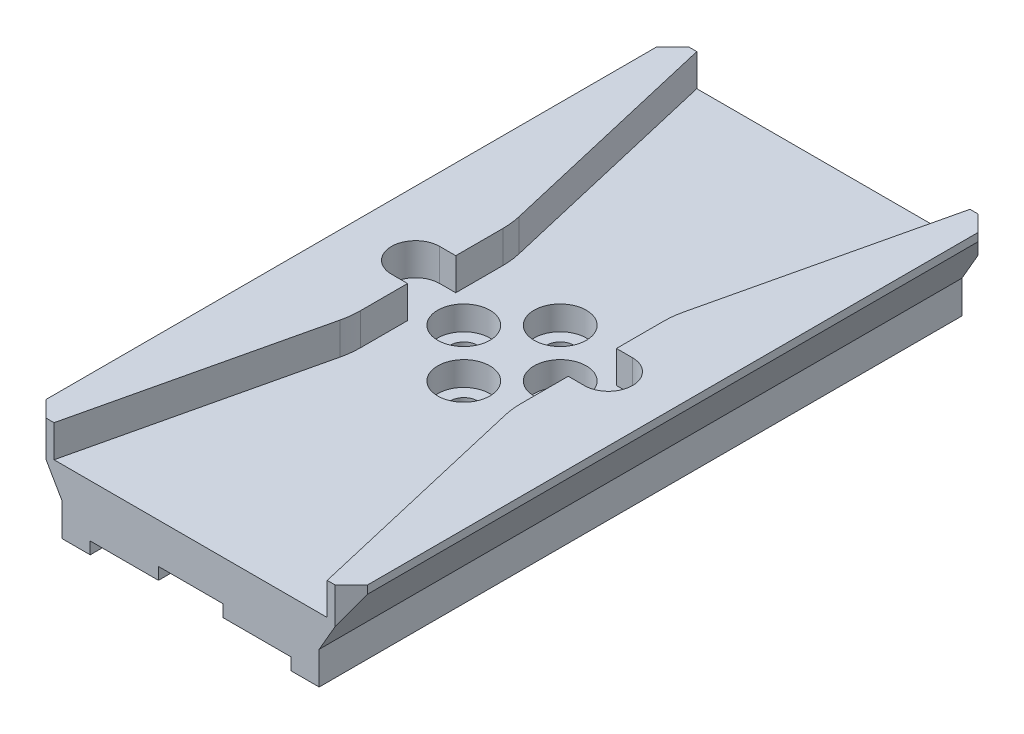
SolidWorks part; units mm, degrees
material "Сплав 2024"
ref_plane "Спереди" through (0, 0, 0) normal (0, 0, 1) x (1, 0, 0)
ref_plane "Сверху" through (0, 0, 0) normal (0, 1, 0) x (1, 0, 0)
ref_plane "Справа" through (0, 0, 0) normal (1, 0, 0) x (0, 0, -1)
sketch "Эскиз1" plane through (0, 0, 0) normal (0, 0, 1) x (1, 0, 0)
  line L0 (-20, 5) -> (-16, -1.9282)
  line L1 (-20, 6) -> (20, 6)
  line L2 (-25.6942, 6) -> (28.5829, 6) construction
  line L3 (-16, -6) -> (16, -6)
  line L4 (0, 6) -> (0, -6) construction
  line L5 (-22.304, 8.9907) -> (-15.6808, -2.4811) construction
  line L7 (-16, -1.9282) -> (-16, -6)
  line L9 (-20, 6) -> (-20, 5)
  line L10 (16, -1.9282) -> (16, -6)
  line L11 (20, 5) -> (16, -1.9282)
  line L12 (20, 6) -> (20, 5)
  point P15 (-20.5774, 6)
  dimension "D1" = 16
  dimension "D2" = 12
  dimension "D3" = 60
  dimension "D4" = 20.5774
  dimension "D6" = 20
  dimension "D7" = 1
extrude "Бобышка-Вытянуть1" add sketch "Эскиз1" along normal blind 80
sketch "Эскиз2" plane through (0, 6, 0) normal (0, 1, 0) x (1, 0, 0)
  line L0 (0, 0) -> (0, -80) construction
  line L1 (20, 0) -> (-20, 0) construction
  line L2 (20, -80) -> (-20, -80) construction
  line L3 (-17, 0) -> (-17, -80) construction
  line L4 (10, -50) -> (17, -80)
  line L5 (-17, 0) -> (-10, -30)
  line L6 (-10, -30) -> (-10, -50)
  line L7 (-10, -50) -> (-17, -80)
  line L8 (10, -30) -> (10, -50)
  line L9 (17, 0) -> (10, -30)
  line L10 (20, -40) -> (-20, -40) construction
  line L11 (-17, 0) -> (17, 0)
  line L12 (17, -80) -> (-17, -80)
  line L20 (-20, -80) -> (-20, 0) construction
  line L21 (20, -80) -> (20, 0) construction
  point P24 (-10, -40)
  dimension "D1" = 10
  dimension "D2" = 3
  dimension "D3" = 20
extrude "Вырез-Вытянуть1" cut sketch "Эскиз2" against normal blind 4
sketch "Эскиз3" plane through (0, 6, 0) normal (0, 1, 0) x (1, 0, 0)
  line L0 (20, -40) -> (-20, -40) construction
  line L4 (-10, -37) -> (-15, -37)
  line L5 (-10, -37) -> (-10, -43)
  line L6 (-10, -43) -> (-15, -43)
  line L7 (-15, -37) -> (-15, -43)
  line L8 (0, 0) -> (0, -80) construction
  line L9 (17, 0) -> (-17, 0) construction
  line L10 (-17, -80) -> (17, -80) construction
  line L11 (10, -37) -> (10, -43)
  line L12 (10, -43) -> (15, -43)
  line L13 (15, -37) -> (15, -43)
  line L14 (10, -37) -> (15, -37)
  line L15 (-10, -30) -> (-10, -50) construction
  line L16 (20, -80) -> (20, 0) construction
  line L17 (-20, -80) -> (-20, 0) construction
  point P12 (-10, -40)
  dimension "D1" = 6
  dimension "D2" = 5
extrude "Вырез-Вытянуть2" [suppressed] cut sketch "Эскиз3" against normal blind 4
fillet "Скругление1" [suppressed] radius 1.5
fillet "Скругление2" radius 10 4 edges at (10, 4, 50) (10, 4, 30) (-10, 4, 30) (-10, 4, 50)
sketch "Эскиз4" plane through (0, 2, 0) normal (0, 1, 0) x (1, 0, 0)
  line L0 (0, 0) -> (0, -80) construction
  line L1 (-17, -80) -> (17, -80) construction
  line L2 (20, -40) -> (-20, -40) construction
  line L5 (20, -80) -> (20, 0) construction
  line L6 (-20, -80) -> (-20, 0) construction
  circle A0 centre (0, -40) radius 6 construction
  dimension "D1" = 12
hole_wizard "Цековка для винта с внутренним шестигранником M31" positions "Эскиз6" profile "Эскиз5" counterbore size "M3" standard "Ansi Metric" end condition through all
sketch "Эскиз6" plane through (0, 2, 0) normal (0, 1, 0) x (1, 0, 0)
  line L0 (0, 0) -> (0, -80) construction
  line L1 (20, -40) -> (-20, -40) construction
  circle A0 centre (0, -40) radius 6 construction
  point P0 (0, -34)
  point P2 (6, -40)
  point P4 (0, -46)
  point P6 (-6, -40)
sketch "Эскиз5" plane through (0, 2, 34) normal (1, 0, 0) x (0, 0, 1)
  line L0 (0, 0) -> (0, 8)
  line L1 (0, 8) -> (1.7, 8)
  line L3 (1.7, 8) -> (1.7, 3)
  line L4 (1.7, 3) -> (3.25, 3)
  line L5 (3.25, 3) -> (3.25, 0)
  line L7 (3.25, 0) -> (0, 0)
  line L11 (0, -6.35) -> (0, 107.95) construction
  dimension "Диаметр сквозного отверстия" = 3.4
  dimension "Глубина сквозного отверстия" = 8
  dimension "Диаметр цековки" = 6.5
  dimension "Глубина цековки" = 3
sketch "Эскиз7" plane through (0, -6, 0) normal (0, -1, 0) x (1, 0, 0)
  line L0 (0, 80) -> (0, 0) construction
  line L2 (-11.5, 77) -> (11.5, 77)
  line L3 (-11.5, 77) -> (-11.5, 51)
  line L5 (-16, 80) -> (16, 80) construction
  line L6 (11.5, 77) -> (11.5, 51)
  line L7 (-11.5, 77) -> (11.5, 51) construction
  line L8 (-11.5, 51) -> (11.5, 77) construction
  arc A0 (-11.5, 51) -> (11.5, 51) centre (0, 19) cw
  point P0 (0, 64)
  dimension "D2" = 26
  dimension "D5" = 45
  dimension "D1" = 3
  dimension "D3" = 23
  dimension "D4" = 26
extrude "Вырез-Вытянуть3" cut sketch "Эскиз7" against normal blind 7
sketch "Эскиз8" plane through (0, 1, 0) normal (0, -1, 0) x (1, 0, 0)
  line L0 (0, 80) -> (0, 0) construction
  line L1 (-16, 80) -> (16, 80) construction
  line L2 (-16, 61.2) -> (16, 61.2) construction
  line L3 (-16, 80) -> (-16, 0) construction
  line L4 (16, 80) -> (16, 0) construction
  line L6 (13.1, 58.95) -> (7.1, 63.45) construction
  line L7 (-13.1, 63.45) -> (-7.1, 63.45)
  line L8 (-13.1, 63.45) -> (-13.1, 58.95)
  line L9 (-13.1, 58.95) -> (-7.1, 58.95)
  line L10 (13.1, 63.45) -> (7.1, 58.95) construction
  line L11 (-13.1, 63.45) -> (-7.1, 58.95) construction
  line L12 (-13.1, 58.95) -> (-7.1, 63.45) construction
  line L13 (13.1, 58.95) -> (7.1, 58.95)
  line L14 (13.1, 63.45) -> (13.1, 58.95)
  line L15 (13.1, 63.45) -> (7.1, 63.45)
  arc A0 (-7.1, 58.95) -> (-7.1, 63.45) centre (-7.1, 61.2) ccw
  arc A1 (7.1, 58.95) -> (7.1, 63.45) centre (7.1, 61.2) cw
  point P17 (-10.1, 61.2)
  point P24 (10.1, 61.2)
  dimension "D1" = 7.1
  dimension "D2" = 4.5
  dimension "D3" = 10.2
  dimension "D4" = 3
extrude "Бобышка-Вытянуть2" add sketch "Эскиз8" along normal blind 3
hole_wizard "Отверстие обработанное метчиком M2.5x0.451" positions "Эскиз10" profile "Эскиз9" tap size "M2.5x0.45" standard "Ansi Metric"
sketch "Эскиз10" plane through (0, -2, 0) normal (0, -1, 0) x (-1, 0, 0)
  point P0 (7.1, -61.2)
  point P2 (-7.1, -61.2)
sketch "Эскиз9" plane through (-7.1, -2, 61.2) normal (1, 0, 0) x (0, 0, -1)
  line L0 (0, 0) -> (0, 3.6159)
  line L1 (0, 3.6159) -> (1.025, 3)
  line L2 (1.025, 3) -> (1.025, 0)
  line L5 (1.025, 0) -> (0, 0)
  line L10 (0, 3.6159) -> (-1.025, 3) construction
  line L11 (0, -6.35) -> (0, 107.95) construction
  dimension "Диаметр сверла" = 2.05
  dimension "Глубина сверла" = 3
  dimension "Угол заточки сверла" = 118
cosmetic thread "Отверстие резьбы7" parameters "D1"=3, "D2"=2.5
cosmetic thread "Отверстие резьбы8" parameters "D1"=3, "D2"=2.5
sketch "Эскиз12" plane through (0, 1, 0) normal (0, -1, 0) x (1, 0, 0)
  line L0 (0, 77) -> (0, 51) construction
  line L1 (11.5, 77) -> (-11.5, 77) construction
  line L2 (-11.5, 51) -> (11.5, 51) construction
  line L3 (-1.8247, 64) -> (1.8247, 64) construction
  line L4 (-13.6614, 76) -> (7.1704, 76) construction
  line L5 (-11.5, 80.8402) -> (-11.5, 69.1924) construction
  line L6 (-11.5, 77) -> (-11.5, 51) construction
  circle A0 centre (-11.5, 76) radius 2
  circle A3 centre (11.5, 76) radius 2
  circle A4 centre (11.5, 52) radius 2
  circle A6 centre (-11.5, 52) radius 2
  point P14 (0, 64)
  dimension "D3" = 4
  dimension "D2" = 1
sketch "Эскиз15" plane through (0, 1, 0) normal (0, -1, 0) x (1, 0, 0)
  line L0 (0, 77) -> (0, 51) construction
  line L1 (11.5, 77) -> (-11.5, 77) construction
  line L2 (-13.8501, 64) -> (13.8501, 64) construction
  line L4 (-11.5, 51) -> (11.5, 51) construction
  line L5 (11.5, 51) -> (11.5, 77) construction
  line L7 (11.5, 77) -> (-11.5, 77) construction
  line L8 (-11.5, 77) -> (-11.5, 63.45) construction
  line L9 (-11.5, 77) -> (-11.5, 51) construction
  circle A0 centre (-11.5, 51) radius 2.5
  circle A1 centre (11.5, 51) radius 2.5
  circle A2 centre (-9, 77) radius 2.5
  circle A3 centre (9, 77) radius 2.5
  point P8 (0, 64)
  dimension "D1" = 5
  dimension "D2" = 5
  dimension "D3" = 5
extrude "Бобышка-Вытянуть5" add sketch "Эскиз15" along normal up to surface (7 mm away) up to face at (0, -6, 64.5009)
fillet "Скругление8" radius 3 12 edges at (11.5, -2.5, 53.5) (9.1178, -2.5, 51.7584) (-9.1178, -2.5, 51.7584) (-11.5, -2.5, 53.5) (-11.5, -0.5, 58.95) (11.5, -0.5, 58.95) (11.5, -0.5, 63.45) (-11.5, -0.5, 63.45) (-11.5, -2.5, 77) (11.5, -2.5, 77) (6.5, -2.5, 77) (-6.5, -2.5, 77)
sketch "Эскиз16" plane through (0, -6, 0) normal (0, -1, 0) x (1, 0, 0)
  line L0 (-16, 80) -> (16, 80) construction
  line L1 (-12.5, 80) -> (12.5, 80)
  line L70 (-12.5, 54.3541) -> (-12.5, 80)
  line L71 (12.5, 54.3541) -> (12.5, 80)
  line L72 (-11.5, 71.5228) -> (-11.5, 55.6098) construction
  line L73 (11.5, 55.6098) -> (11.5, 71.5228) construction
  arc A0 (7.2531, 52.2211) -> (-7.2531, 52.2211) centre (0, 19) ccw construction
  arc A1 (7.2531, 52.2211) -> (-7.2531, 52.2211) centre (0, 19) ccw construction
  arc A2 (8.0001, 51.0194) -> (-8.0001, 51.0194) centre (0, 19) ccw
  arc A3 (7.0398, 51.2441) -> (-7.0398, 51.2441) centre (0, 19) ccw construction
  arc A42 (-12.5, 54.3541) -> (-8.0001, 51.0194) centre (-11.5, 51) ccw
  arc A43 (8.0001, 51.0194) -> (12.5, 54.3541) centre (11.5, 51) ccw
  dimension "D3" = 7
  dimension "D4" = 7
  dimension "D6" = 1
  dimension "D7" = 1
  dimension "D2" = 1
extrude "Вырез-Вытянуть6" cut sketch "Эскиз16" against normal blind 1.5
fillet "Скругление9" radius 3 4 edges at (12.5, -5.25, 54.3541) (8.0001, -5.25, 51.0194) (-8.0001, -5.25, 51.0194) (-12.5, -5.25, 54.3541)
hole_wizard "Отверстие обработанное метчиком M3x0.52" positions "Эскиз19" profile "Эскиз18" tap size "M3x0.5" standard "Ansi Metric"
sketch "Эскиз19" plane through (0, -4.5, 0) normal (0, -1, 0) x (-1, 0, 0)
  point P0 (11.5, -51)
  point P3 (-11.5, -51)
  point P6 (-9, -77)
  point P9 (9, -77)
sketch "Эскиз18" plane through (-11.5, -4.5, 51) normal (1, 0, 0) x (0, 0, -1)
  line L0 (0, 0) -> (0, 6.2501)
  line L1 (0, 6.2501) -> (1.25, 5.499)
  line L2 (1.25, 5.499) -> (1.25, 0)
  line L5 (1.25, 0) -> (0, 0)
  line L10 (0, 6.2501) -> (-1.25, 5.499) construction
  line L11 (0, -6.35) -> (0, 107.95) construction
  dimension "Диаметр сверла" = 2.5
  dimension "Глубина сверла" = 5.499
  dimension "Угол заточки сверла" = 118
cosmetic thread "Отверстие резьбы9" parameters "D1"=5.5, "D2"=3
cosmetic thread "Отверстие резьбы10" parameters "D1"=5.5, "D2"=3
cosmetic thread "Отверстие резьбы11" parameters "D1"=5.5, "D2"=3
cosmetic thread "Отверстие резьбы12" parameters "D1"=5.5, "D2"=3
sketch "Эскиз20" plane through (0, -4.5, 0) normal (0, -1, 0) x (1, 0, 0)
  line L0 (0, 80) -> (0, 67.2176) construction
  line L1 (12.5, 80) -> (-12.5, 80) construction
  line L2 (-4.3902, 77) -> (4.3902, 77) construction
  line L3 (-4, 80) -> (4, 80)
  line L4 (-4, 80) -> (-4, 77)
  line L5 (-4, 77) -> (4, 77)
  line L6 (4, 80) -> (4, 77)
  line L7 (-4, 80) -> (4, 77) construction
  line L8 (-4, 77) -> (4, 80) construction
  point P5 (0, 78.5)
  dimension "D1" = 8
extrude "Вырез-Вытянуть7" cut sketch "Эскиз20" against normal blind 1.5
sketch "Эскиз21" plane through (0, -2, 0) normal (0, -1, 0) x (1, 0, 0)
  line L0 (11.5, 61.2) -> (-11.5, 61.2) construction
  line L1 (11.5, 55.95) -> (11.5, 66.45) construction
  line L2 (-11.5, 55.95) -> (-11.5, 66.45) construction
  line L3 (0, 53.0037) -> (0, 77) construction
  line L4 (4.3902, 77) -> (-4.3902, 77) construction
  line L6 (-5.5, 63.7) -> (5.5, 63.7)
  line L7 (-5.5, 63.7) -> (-5.5, 58.7)
  line L8 (-5.5, 58.7) -> (5.5, 58.7)
  line L9 (5.5, 63.7) -> (5.5, 58.7)
  line L10 (-5.5, 63.7) -> (5.5, 58.7) construction
  line L11 (-5.5, 58.7) -> (5.5, 63.7) construction
  arc A0 (7.2531, 52.2211) -> (-7.2531, 52.2211) centre (0, 19) ccw construction
  point P13 (0, 61.2)
  dimension "D1" = 11
  dimension "D2" = 5
extrude "Вырез-Вытянуть8" cut sketch "Эскиз21" against normal up to surface (3 mm away) up to face at (0, 1, 62.8736)
ref_plane "Плоскость1" through (0, 0, 40) normal (0, 0, 1) x (1, 0, 0)
mirror "Зеркальное отражение1" about plane through (0, 0, 40) normal (0, 0, 1) of "Вырез-Вытянуть3"
fillet "Скругление10" radius 3 4 edges at (11.5, -2.5, 3) (-11.5, -2.5, 3) (-11.5, -2.5, 29) (11.5, -2.5, 29)
sketch "Эскиз23" plane through (0, 6, 0) normal (0, 1, 0) x (1, 0, 0)
  line L0 (-17, 0) -> (-20, 0) construction
  line L1 (-20, -80) -> (-20, 0) construction
  line L2 (-17.464, 0) -> (-20, 0)
  line L3 (-20, 0) -> (-20, -2.536)
  line L4 (0, 0) -> (0, -80) construction
  line L5 (-17, -80) -> (17, -80) construction
  line L6 (20, -40) -> (-20, -40) construction
  line L7 (20, -80) -> (20, 0) construction
  line L8 (20, 0) -> (20, -2.536)
  line L9 (17.464, 0) -> (20, 0)
  line L10 (20, -2.536) -> (17.464, 0)
  line L11 (20, -77.464) -> (17.464, -80)
  line L12 (17.464, -80) -> (20, -80)
  line L13 (20, -80) -> (20, -77.464)
  line L14 (-20, -2.536) -> (-17.464, 0)
  line L15 (-20, -77.464) -> (-17.464, -80)
  line L16 (-20, -80) -> (-20, -77.464)
  line L17 (-17.464, -80) -> (-20, -80)
  dimension "D1" = 45
extrude "Вырез-Вытянуть10" [suppressed] cut sketch "Эскиз23" against normal through all
fillet "Скругление14" [suppressed] radius 1.5
chamfer "Фаска1" distance 2 angle 45 4 edges at (-20, 5.5, 80) (20, 5.5, 80) (20, 5.5, 0) (-20, 5.5, 0)
sketch "Эскиз24" plane through (0, 6, 0) normal (0, 1, 0) x (1, 0, 0)
  line L0 (-20, -40) -> (20, -40) construction
  line L1 (-20, -78) -> (-20, -2) construction
  line L2 (20, -78) -> (20, -2) construction
  line L3 (-12, -40) -> (-8, -40) construction
  line L4 (-12, -37) -> (-8, -37)
  line L5 (-12, -43) -> (-8, -43)
  line L6 (-10, -31.1512) -> (-10, -48.8488) construction
  line L7 (0, 0) -> (0, -80) construction
  line L8 (-17, -80) -> (17, -80) construction
  line L9 (12, -40) -> (8, -40) construction
  line L10 (12, -37) -> (8, -37)
  line L11 (12, -43) -> (8, -43)
  arc A0 (-12, -37) -> (-12, -43) centre (-12, -40) ccw
  arc A1 (-8, -43) -> (-8, -37) centre (-8, -40) ccw
  arc A2 (12, -37) -> (12, -43) centre (12, -40) cw
  arc A3 (8, -43) -> (8, -37) centre (8, -40) cw
  point P8 (-10, -40)
  point P22 (10, -40)
  dimension "D1" = 3
  dimension "D2" = 2
extrude "Вырез-Вытянуть11" cut sketch "Эскиз24" against normal up to surface (4 mm away) up to face at (0, 2, 37.25)
